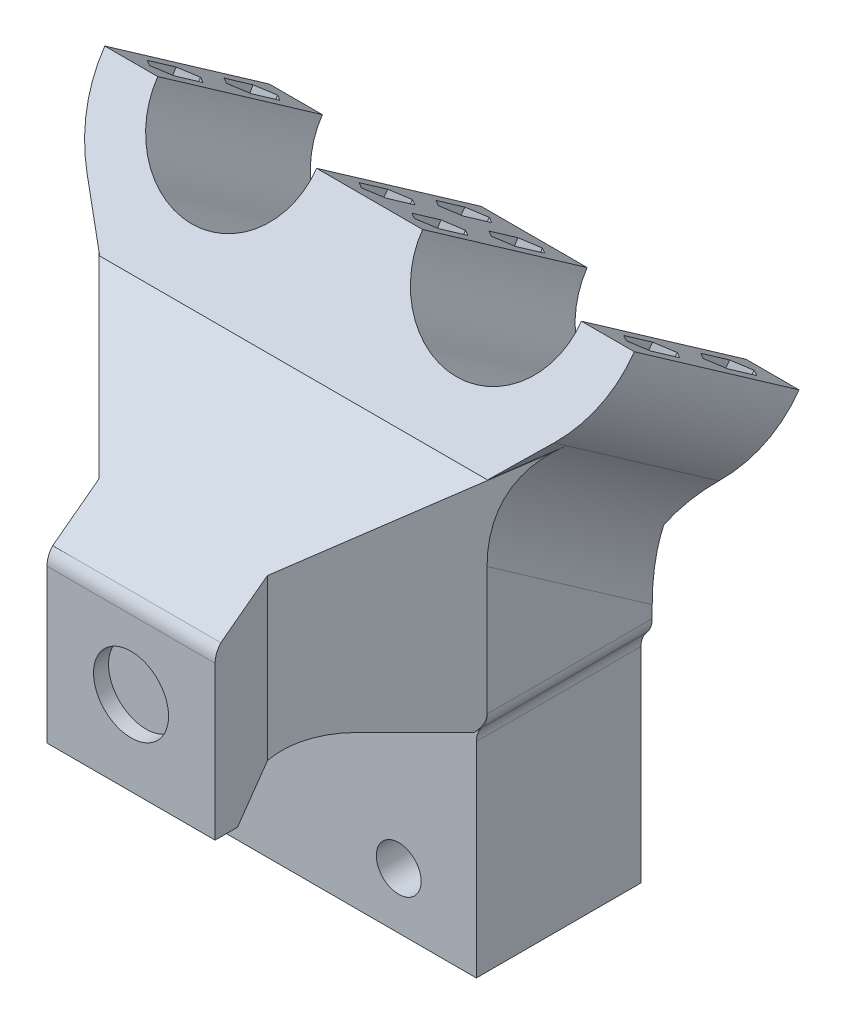
SolidWorks part; units mm, degrees
ref_plane "Alzado" through (0, 0, 0) normal (0, 0, 1) x (1, 0, 0)
ref_plane "Planta" through (0, 0, 0) normal (0, 1, 0) x (1, 0, 0)
ref_plane "Vista lateral" through (0, 0, 0) normal (1, 0, 0) x (0, 0, -1)
sketch "Croquis1" plane through (0, 0, 0) normal (0, 0, 1) x (1, 0, 0)
  line L0 (21.971, 0) -> (21.971, 6.2992) construction
  line L1 (0, 0) -> (43.942, 0)
  line L2 (0, 0) -> (0, 36.4389)
  line L3 (0, 36.4389) -> (43.942, 36.4389)
  line L4 (43.942, 0) -> (43.942, 36.4389)
  circle A0 centre (10.0647, 6.35) radius 2.54
  circle A1 centre (33.8772, 6.35) radius 2.54
  dimension "D1" = 5.08
  dimension "D3" = 3.81
  dimension "D4" = 32.6289
  dimension "D5" = 43.942
  dimension "D6" = 23.8125
extrude "Saliente-Extruir1" add sketch "Croquis1" along normal blind 18.6531
sketch "Croquis3" plane through (0, 0, 0) normal (-1, 0, 0) x (0, 0, 1)
  line L0 (0, 36.4389) -> (18.6531, 49.4999)
  line L1 (0, 36.4389) -> (-7.8285, 47.6192) construction
  line L2 (18.6531, 49.4999) -> (18.6531, 36.4389)
  line L3 (0, 36.4389) -> (18.6531, 36.4389)
  dimension "D1" = 35
ref_plane "Plano2" through (0, 11.988, 17.1207) normal (0, 0.5736, 0.8192) x (1, 0, 0)
extrude "Saliente-Extruir2" add sketch "Croquis3" against normal up to vertex (43.942 mm away)
sketch "Croquis5" plane through (0, 11.988, 17.1207) normal (0, 0.5736, 0.8192) x (1, 0, 0)
  line L0 (21.971, 29.849) -> (21.971, 44.849) construction
  line L1 (43.942, 29.849) -> (0, 29.849) construction
  line L2 (6.971, 44.849) -> (12.971, 44.849)
  line L3 (12.971, 44.849) -> (30.971, 44.849)
  line L4 (30.971, 44.849) -> (36.971, 44.849)
  line L5 (6.971, 44.849) -> (0, 29.849)
  line L6 (0, 29.849) -> (43.942, 29.849)
  line L7 (43.942, 29.849) -> (36.971, 44.849)
  circle A0 centre (21.971, 44.849) radius 15
  circle A1 centre (21.971, 44.849) radius 9
  dimension "D1" = 18
  dimension "D2" = 6
extrude "Saliente-Extruir3" add sketch "Croquis5" along normal up to vertex (22.7713 mm away) separate body contours A0 L0 A1 L2 | L0 A0 L4 A1 | A0 L5 L6 | A0 L6 L7
sketch "Croquis7" plane through (0, 36.7381, -25.7243) normal (0, 0.8192, -0.5736) x (1, 0, 0)
  line L0 (9.971, -20.9005) -> (9.971, -23.4405) construction
  line L1 (8.471, -28.9405) -> (8.471, -24.9405)
  line L2 (11.471, -28.9405) -> (11.471, -24.9405)
  line L3 (8.471, -28.9405) -> (9.971, -30.4405)
  line L4 (9.971, -30.4405) -> (11.471, -28.9405)
  line L5 (11.471, -24.9405) -> (9.971, -23.4405)
  line L6 (9.971, -23.4405) -> (8.471, -24.9405)
  line L7 (6.971, -20.9005) -> (12.971, -20.9005) construction
  line L8 (6.971, -32.2861) -> (11.7793, -32.2861) construction
  line L9 (6.971, -43.6717) -> (6.971, -20.9005) construction
  line L10 (9.971, -41.1317) -> (8.471, -39.6317)
  line L11 (11.471, -39.6317) -> (9.971, -41.1317)
  line L12 (9.971, -34.1317) -> (11.471, -35.6317)
  line L13 (8.471, -35.6317) -> (9.971, -34.1317)
  line L14 (11.471, -35.6317) -> (11.471, -39.6317)
  line L15 (8.471, -35.6317) -> (8.471, -39.6317)
  line L16 (12.971, -43.6717) -> (30.971, -43.6717) construction
  line L17 (12.971, -43.6717) -> (30.971, -43.6717) construction
  line L18 (21.971, -43.6717) -> (21.971, -38.4515) construction
  point P2 (11.3797, -24.6032)
  point P10 (11.3797, -39.969)
  dimension "D1" = 4
  dimension "D2" = 3
  dimension "D3" = 2.54
revolve "Cortar-Revolución1" cut sketch "Croquis7" angle 360 about L18
sketch "Croquis11" plane through (0, 0, 18.6531) normal (0, 0, 1) x (1, 0, 0)
  line L0 (21.971, 49.4999) -> (21.971, 0) construction
  line L1 (0, 49.4999) -> (43.942, 49.4999) construction
  line L2 (0, 0) -> (43.942, 0) construction
  line L4 (12.446, 24.765) -> (31.496, 24.765)
  line L5 (12.446, 24.765) -> (12.446, 36.195)
  line L6 (12.446, 36.195) -> (31.496, 36.195)
  line L7 (31.496, 24.765) -> (31.496, 36.195)
  line L8 (12.446, 24.765) -> (31.496, 36.195) construction
  line L9 (12.446, 36.195) -> (31.496, 24.765) construction
  circle A0 centre (21.971, 30.48) radius 4 construction
  point P6 (21.971, 30.48)
  dimension "D2" = 8
  dimension "D1" = 24.765
  dimension "D3" = 11.43
  dimension "D4" = 19.05
extrude "Saliente-Extruir5" add sketch "Croquis11" along normal blind 8.89
sketch "Croquis12" plane through (0, 0, 27.5431) normal (0, 0, 1) x (1, 0, 0)
  line L0 (31.496, 36.195) -> (12.446, 36.195) construction
  line L1 (12.446, 36.195) -> (12.446, 24.765) construction
  circle A0 centre (21.971, 30.48) radius 4
  point P5 (21.971, 36.195)
  point P8 (12.446, 30.48)
  dimension "D1" = 8
sketch "Croquis13" plane through (12.446, 0, 0) normal (-1, 0, 0) x (0, 0, 1)
  line L0 (27.5431, 24.765) -> (34.7036, 22.1588)
  line L1 (34.7036, 22.1588) -> (38.3771, 32.2518)
  line L2 (38.3771, 32.2518) -> (27.5431, 36.195)
  line L3 (27.5431, 36.195) -> (27.5431, 24.765)
  line L4 (27.5431, 24.765) -> (18.6531, 24.765) construction
  dimension "D1" = 160
  dimension "D2" = 7.62
ref_plane "Plano3" through (0, 0, 36.4331) normal (0, 0, 1) x (1, 0, 0)
sketch "Croquis17" plane through (12.446, 0, 0) normal (-1, 0, 0) x (0, 0, 1)
  line L0 (27.5431, 24.765) -> (27.5431, 17.145)
  line L1 (27.5431, 17.145) -> (37.0728, 17.145)
  line L2 (37.0728, 17.145) -> (37.0728, 36.195)
  line L3 (37.0728, 36.195) -> (27.5431, 36.195)
  line L4 (27.5431, 36.195) -> (27.5431, 24.765)
  dimension "D1" = 19.05
  dimension "D2" = 9.5297
extrude "Saliente-Extruir7" add sketch "Croquis17" against normal up to surface (19.05 mm away) up to face at (31.496, 30.48, 23.0981)
sketch "Croquis18" plane through (0, 0, 37.0728) normal (0, 0, 1) x (1, 0, 0)
  line L0 (21.971, 17.145) -> (21.971, 26.67) construction
  line L1 (21.971, 26.67) -> (12.446, 26.67) construction
  line L2 (12.446, 17.145) -> (12.446, 36.195) construction
  line L3 (31.496, 17.145) -> (12.446, 17.145) construction
  line L4 (21.971, 22.42) -> (21.971, 30.92) construction
  circle A0 centre (21.971, 26.67) radius 4.25
  dimension "D1" = 8.5
extrude "Cortar-Extruir7" cut sketch "Croquis18" against normal blind 1.7
sketch "Croquis19" plane through (31.496, 0, 0) normal (1, 0, 0) x (0, 0, -1)
  line L0 (-27.5431, 20.955) -> (-23.0981, 24.765)
  line L1 (-27.5431, 17.145) -> (-27.5431, 24.765) construction
  line L2 (-27.5431, 24.765) -> (-18.6531, 24.765) construction
  line L3 (-23.0981, 24.765) -> (-27.5431, 24.765)
  line L4 (-27.5431, 24.765) -> (-27.5431, 20.955)
extrude "Saliente-Extruir8" add sketch "Croquis19" against normal up to surface (19.05 mm away) up to face at (12.446, 26.035, 27.7564)
sketch "Croquis20" plane through (12.446, 0, 0) normal (-1, 0, 0) x (0, 0, 1)
  line L0 (18.6531, 24.75) -> (27.5431, 24.75)
  line L1 (18.6531, 49.4999) -> (18.6531, 0) construction
  line L3 (18.6531, 24.75) -> (18.6531, 17.145)
  line L4 (18.6531, 17.145) -> (34.5328, 17.145)
  line L8 (29.2078, 24.75) -> (27.5431, 24.75)
  line L9 (27.5431, 17.145) -> (37.0728, 17.145) construction
  line L10 (29.2078, 24.75) -> (34.5328, 17.145)
  dimension "D1" = 2.54
  dimension "D2" = 125
extrude "Cortar-Extruir8" cut sketch "Croquis20" against normal through all
fillet "Redondeo10" radius 5.969 1 edges at (21.971, 24.75, 29.2078)
fillet "Redondeo11" [suppressed] radius 0.762
chamfer "Chaflán1" distance 13.3049 distance2 17.7724 1 edges at (21.971, 36.195, 18.6531)
chamfer "Chaflán2" distance 12.5016 angle 45 2 edges at (31.496, 37.1325, 18.6531) (12.446, 37.1325, 18.6531)
fillet "Redondeo12" radius 2.54 1 edges at (21.971, 36.195, 37.0728)
sketch "Croquis21" plane through (0, 36.7381, -25.7243) normal (0, 0.8192, -0.5736) x (1, 0, 0)
  line L0 (9.971, -20.9005) -> (9.971, -43.6717) construction
  line L1 (6.971, -20.9005) -> (12.971, -20.9005) construction
  line L2 (0, -43.6717) -> (43.942, -43.6717) construction
  line L3 (9.971, -32.2861) -> (33.971, -32.2861) construction
  line L4 (33.971, -32.2861) -> (33.971, -20.9005) construction
  line L5 (30.971, -20.9005) -> (36.971, -20.9005) construction
  line L7 (0, -43.6717) -> (43.942, -43.6717)
  line L8 (0, -43.6717) -> (0, -20.9005)
  line L9 (0, -20.9005) -> (43.942, -20.9005)
  line L10 (43.942, -43.6717) -> (43.942, -20.9005)
  line L11 (0, -43.6717) -> (43.942, -20.9005) construction
  line L12 (0, -20.9005) -> (43.942, -43.6717) construction
  point P4 (21.971, -32.2861)
extrude "Cortar-Extruir9" cut sketch "Croquis21" against normal blind 14.986
sketch "Croquis22" plane through (0, 11.988, 17.1207) normal (0, 0.5736, 0.8192) x (1, 0, 0)
  line L0 (6.971, 50.3468) -> (6.971, 44.8505) construction
  line L1 (-8.029, 44.8505) -> (-2.029, 44.8505)
  line L2 (-2.029, 44.8505) -> (15.971, 44.8505)
  line L3 (15.971, 44.8505) -> (21.971, 44.8505)
  line L7 (21.971, 29.849) -> (21.971, 8.7564) construction
  line L8 (43.942, 29.849) -> (0, 29.849) construction
  line L9 (31.496, 8.7564) -> (12.446, 8.7564) construction
  line L13 (36.971, 50.3468) -> (36.971, 44.8505) construction
  line L14 (0, 29.849) -> (-4.496, 35.1805)
  line L15 (43.942, 29.849) -> (48.438, 35.1805)
  line L17 (27.971, 44.8505) -> (21.971, 44.8505)
  line L18 (45.971, 44.8505) -> (27.971, 44.8505)
  line L19 (51.971, 44.8505) -> (45.971, 44.8505)
  line L21 (0, 29.849) -> (43.942, 29.849)
  line L23 (43.942, 29.849) -> (43.942, 29.783) construction
  line L24 (43.942, 29.849) -> (43.9355, 29.863) construction
  arc A0 (21.971, 44.8505) -> (-4.496, 35.1805) centre (6.971, 44.8505) ccw
  circle A1 centre (6.971, 44.8505) radius 9
  circle A2 centre (36.971, 44.8505) radius 9
  arc A3 (21.971, 44.8505) -> (48.438, 35.1805) centre (36.971, 44.8505) cw
  dimension "D1" = 18
  dimension "D2" = 6
  dimension "D4" = 25.4
  dimension "D5" = 15.0015
extrude "Saliente-Extruir9" add sketch "Croquis22" along normal up to vertex
ref_plane "Plano4" through (21.971, 0, 0) normal (-1, 0, 0) x (0, 0, 1)
sketch "Croquis23" plane through (0, 36.7393, -25.7252) normal (0, 0.8192, -0.5736) x (1, 0, 0)
  line L0 (48.971, -20.9005) -> (48.971, -23.4405) construction
  line L1 (47.447, -28.9645) -> (47.447, -24.9645)
  line L2 (50.495, -28.9645) -> (50.495, -24.9645)
  line L3 (47.447, -28.9645) -> (48.971, -30.4885)
  line L4 (48.971, -30.4885) -> (50.495, -28.9645)
  line L5 (50.495, -24.9645) -> (48.971, -23.4405)
  line L6 (48.971, -23.4405) -> (47.447, -24.9645)
  line L7 (51.971, -20.9005) -> (45.971, -20.9005) construction
  line L8 (51.971, -32.2861) -> (45.971, -32.2861) construction
  line L9 (51.971, -43.6717) -> (51.971, -20.9005) construction
  line L10 (45.971, -43.6717) -> (45.971, -20.9005) construction
  line L11 (48.971, -43.6717) -> (48.971, -41.1317) construction
  line L12 (48.971, -41.1317) -> (47.447, -39.6077)
  line L13 (50.495, -39.6077) -> (48.971, -41.1317)
  line L14 (48.971, -34.0837) -> (50.495, -35.6077)
  line L15 (47.447, -35.6077) -> (48.971, -34.0837)
  line L16 (50.495, -35.6077) -> (50.495, -39.6077)
  line L17 (47.447, -35.6077) -> (47.447, -39.6077)
  line L18 (36.971, -20.9005) -> (36.971, -43.6717) construction
  line L19 (45.971, -20.9005) -> (27.971, -20.9005) construction
  line L20 (43.942, -43.6717) -> (0, -43.6717) construction
  line L21 (21.971, -20.9005) -> (21.971, -43.6717) construction
  line L22 (27.971, -20.9005) -> (15.971, -20.9005) construction
  line L23 (-5.029, -43.6717) -> (-5.029, -41.1317) construction
  line L24 (-8.029, -32.2861) -> (-2.029, -32.2861) construction
  line L25 (-5.029, -20.9005) -> (-5.029, -23.4405) construction
  line L26 (-3.505, -35.6077) -> (-3.505, -39.6077)
  line L27 (-6.553, -35.6077) -> (-6.553, -39.6077)
  line L28 (-3.505, -35.6077) -> (-5.029, -34.0837)
  line L29 (-5.029, -34.0837) -> (-6.553, -35.6077)
  line L30 (-6.553, -39.6077) -> (-5.029, -41.1317)
  line L31 (-5.029, -41.1317) -> (-3.505, -39.6077)
  line L32 (-5.029, -23.4405) -> (-3.505, -24.9645)
  line L33 (-6.553, -24.9645) -> (-5.029, -23.4405)
  line L34 (-5.029, -30.4885) -> (-6.553, -28.9645)
  line L35 (-3.505, -28.9645) -> (-5.029, -30.4885)
  line L36 (-6.553, -28.9645) -> (-6.553, -24.9645)
  line L37 (-3.505, -28.9645) -> (-3.505, -24.9645)
  point P2 (52.9971, -29.5131)
  point P49 (-9.0551, -29.5131)
  dimension "D1" = 4
  dimension "D2" = 2.54
  dimension "D3" = 90
  dimension "D4" = 3.048
sketch "Croquis24" plane through (0, 36.7393, -25.7252) normal (0, 0.8192, -0.5736) x (1, 0, 0)
  line L0 (6.971, -20.9005) -> (6.971, -43.6717) construction
  line L1 (15.971, -20.9005) -> (-2.029, -20.9005) construction
  line L2 (-2.029, -43.6717) -> (15.971, -43.6717) construction
  line L3 (36.971, -20.9005) -> (36.971, -43.6717) construction
  line L4 (45.971, -20.9005) -> (27.971, -20.9005) construction
  line L5 (27.971, -43.6717) -> (45.971, -43.6717) construction
revolve "Cortar-Revolución2" cut sketch "Croquis23" angle 360 about L18
sketch "Croquis25" plane through (0, 0, 0) normal (0, 0, 1) x (1, 0, 0)
  line L0 (48.971, -20.9005) -> (48.971, -23.4405) construction
  line L1 (47.447, -28.9645) -> (47.447, -24.9645)
  line L2 (50.495, -28.9645) -> (50.495, -24.9645)
  line L3 (47.447, -28.9645) -> (48.971, -30.4885)
  line L4 (48.971, -30.4885) -> (50.495, -28.9645)
  line L5 (50.495, -24.9645) -> (48.971, -23.4405)
  line L6 (48.971, -23.4405) -> (47.447, -24.9645)
  line L8 (51.971, -32.2861) -> (45.971, -32.2861) construction
  line L11 (48.971, -43.6717) -> (48.971, -41.1317) construction
  line L12 (48.971, -41.1317) -> (47.447, -39.6077)
  line L13 (50.495, -39.6077) -> (48.971, -41.1317)
  line L14 (48.971, -34.0837) -> (50.495, -35.6077)
  line L15 (47.447, -35.6077) -> (48.971, -34.0837)
  line L16 (50.495, -35.6077) -> (50.495, -39.6077)
  line L17 (47.447, -35.6077) -> (47.447, -39.6077)
  line L18 (36.971, -20.9005) -> (36.971, -43.6717) construction
  line L21 (21.971, -20.9005) -> (21.971, -43.6717) construction
  line L23 (-5.029, -43.6717) -> (-5.029, -41.1317) construction
  line L24 (-8.029, -32.2861) -> (-2.029, -32.2861) construction
  line L25 (-5.029, -20.9005) -> (-5.029, -23.4405) construction
  line L26 (-3.505, -35.6077) -> (-3.505, -39.6077)
  line L27 (-6.553, -35.6077) -> (-6.553, -39.6077)
  line L28 (-3.505, -35.6077) -> (-5.029, -34.0837)
  line L29 (-5.029, -34.0837) -> (-6.553, -35.6077)
  line L30 (-6.553, -39.6077) -> (-5.029, -41.1317)
  line L31 (-5.029, -41.1317) -> (-3.505, -39.6077)
  line L32 (-5.029, -23.4405) -> (-3.505, -24.9645)
  line L33 (-6.553, -24.9645) -> (-5.029, -23.4405)
  line L34 (-5.029, -30.4885) -> (-6.553, -28.9645)
  line L35 (-3.505, -28.9645) -> (-5.029, -30.4885)
  line L36 (-6.553, -28.9645) -> (-6.553, -24.9645)
  line L37 (-3.505, -28.9645) -> (-3.505, -24.9645)
  point P2 (52.9971, -29.5131)
  point P49 (-9.0551, -29.5131)
  dimension "D1" = 4
  dimension "D2" = 2.54
  dimension "D3" = 90
  dimension "D4" = 3.048
sketch "Croquis26" plane through (0, 36.7393, -25.7252) normal (0, 0.8192, -0.5736) x (1, 0, 0)
  line L0 (-8.029, -20.9005) -> (-2.029, -20.9005) construction
  line L7 (-8.029, -32.2861) -> (-2.029, -32.2861) construction
  line L8 (-8.029, -43.6717) -> (-8.029, -20.9005) construction
  line L15 (-2.029, -43.6717) -> (-2.029, -20.9005) construction
  line L16 (-5.029, -43.6717) -> (-5.029, -41.1317) construction
  line L17 (-3.505, -35.6077) -> (-3.505, -39.6077)
  line L18 (-6.553, -35.6077) -> (-6.553, -39.6077)
  line L19 (-5.029, -20.9005) -> (-5.029, -23.4405) construction
  line L26 (-5.029, -23.4405) -> (-3.505, -24.9645)
  line L27 (-6.553, -24.9645) -> (-5.029, -23.4405)
  line L28 (-5.029, -30.4885) -> (-6.553, -28.9645)
  line L29 (-3.505, -28.9645) -> (-5.029, -30.4885)
  line L30 (-6.553, -28.9645) -> (-6.553, -24.9645)
  line L31 (-3.505, -28.9645) -> (-3.505, -24.9645)
  line L32 (-3.505, -35.6077) -> (-5.029, -34.0837)
  line L33 (-5.029, -34.0837) -> (-6.553, -35.6077)
  line L34 (-6.553, -39.6077) -> (-5.029, -41.1317)
  line L35 (-5.029, -41.1317) -> (-3.505, -39.6077)
  line L36 (-2.029, -32.2861) -> (15.971, -32.2861) construction
  line L37 (15.971, -43.6717) -> (15.971, -20.9005) construction
  line L38 (6.971, -20.9005) -> (6.971, -43.6717) construction
  line L39 (-2.029, -43.6717) -> (15.971, -43.6717) construction
  point P23 (6.971, -32.2861)
  point P37 (-40.8311, -27.3721)
  dimension "D1" = 4
  dimension "D2" = 3.048
  dimension "D3" = 2.54
  dimension "D4" = 90
  dimension "D5" = 90
  dimension "D6" = 135
  dimension "D7" = 135
  dimension "D8" = 135
  dimension "D9" = 2.1553
  dimension "D10" = 2.1553
  dimension "D11" = 2.1553
revolve "Cortar-Revolución3" cut sketch "Croquis26" angle 360 about L38
fillet "Redondeo13" radius 19.05 2 edges at (0, 42.9694, 9.3266) (43.942, 42.9694, 9.3266)
sketch "Croquis27" plane through (0, 0, 0) normal (-1, 0, 0) x (0, 0, 1)
  line L0 (18.6531, 24.765) -> (18.6531, 0) construction
  line L1 (0, 0) -> (18.6531, 0)
  line L2 (0, 0) -> (0, 25.4)
  line L3 (0, 25.4) -> (18.6531, 25.4)
  line L4 (18.6531, 0) -> (18.6531, 25.4)
  dimension "D1" = 25.4
extrude "Cortar-Extruir10" cut sketch "Croquis27" against normal blind 1.27
fillet "Redondeo14" radius 2.54 1 edges at (1.27, 25.4, 9.3266)
fillet "Redondeo15" radius 2.54 1 edges at (0, 25.4, 9.3266)
sketch "Croquis28" plane through (43.942, 0, 0) normal (1, 0, 0) x (0, 0, -1)
  line L0 (0, 0) -> (0, 27.9422) construction
  line L1 (-18.6531, 0) -> (0, 0)
  line L2 (-18.6531, 0) -> (-18.6531, 25.4)
  line L3 (-18.6531, 25.4) -> (0, 25.4)
  line L4 (0, 0) -> (0, 25.4)
  dimension "D1" = 25.4
extrude "Cortar-Extruir11" cut sketch "Croquis28" against normal blind 1.27
fillet "Redondeo16" radius 2.54 1 edges at (42.672, 25.4, 9.3266)
fillet "Redondeo17" radius 2.54 1 edges at (43.942, 25.4, 9.3266)
sketch "Croquis29" plane through (0, 0, 0) normal (0, 0, -1) x (-1, 0, 0)
  line L0 (-43.942, 26.5604) -> (-43.942, 24.765)
  line L1 (-43.942, 24.765) -> (-43.2112, 24.765)
  line L2 (0, 26.5604) -> (0, 24.765)
  line L3 (0, 24.765) -> (-0.7308, 24.765)
  arc A0 (-43.942, 26.5604) -> (-43.2112, 24.765) centre (-41.3712, 26.5604) ccw
  arc A1 (0, 26.5604) -> (-0.7308, 24.765) centre (-2.5708, 26.5604) cw
extrude "Cortar-Extruir12" cut sketch "Croquis29" against normal blind 21.59
